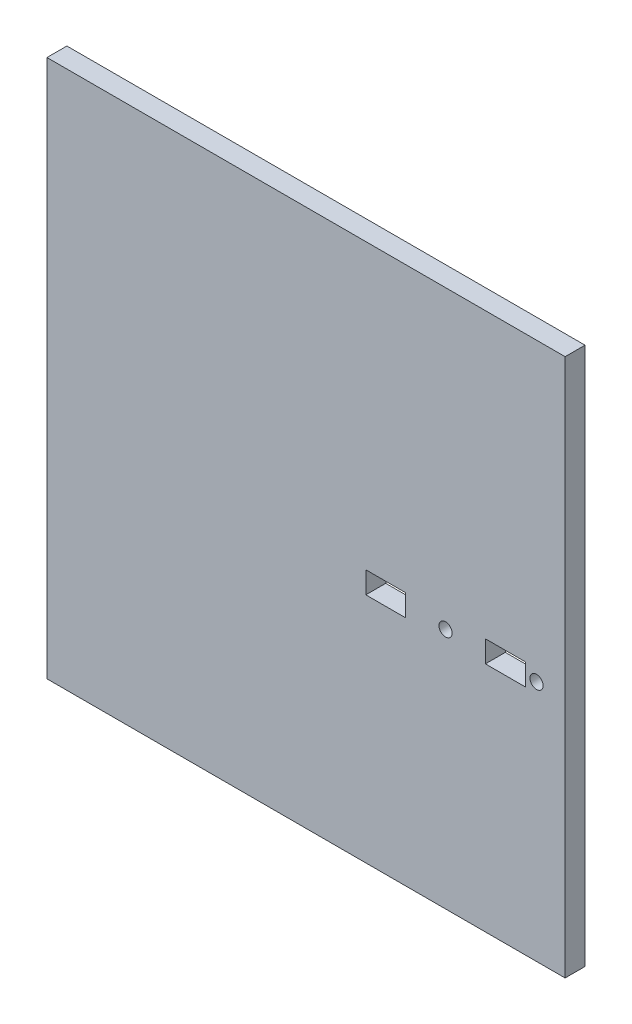
SolidWorks part; units mm, degrees
ref_plane "Front Plane" through (0, 0, 0) normal (0, 0, 1) x (1, 0, 0)
ref_plane "Top Plane" through (0, 0, 0) normal (0, 1, 0) x (1, 0, 0)
ref_plane "Right Plane" through (0, 0, 0) normal (1, 0, 0) x (0, 0, -1)
sketch "Sketch1" plane through (0, 0, 0) normal (0, 0, 1) x (1, 0, 0)
  line L0 (-6.35, 155.575) -> (-6.35, -15.875) construction
  line L1 (158.75, 155.575) -> (-6.35, 155.575)
  line L2 (158.75, 155.575) -> (158.75, -15.875)
  line L3 (158.75, -15.875) -> (-6.35, -15.875)
  line L4 (-6.35, 155.575) -> (-6.35, -15.875)
  line L6 (0, -15.875) -> (-6.35, -15.875) construction
extrude "Boss-Extrude1" add sketch "Sketch1" along normal blind 6.35
sketch "Sketch2" plane through (0, 0, 6.35) normal (0, 0, 1) x (1, 0, 0)
  line L0 (158.75, 40.3225) -> (69.85, 40.3225) construction
  line L1 (95.25, 65.0258) -> (107.95, 65.0258)
  line L2 (95.25, 65.0258) -> (95.25, 58.1025)
  line L3 (95.25, 58.1025) -> (107.95, 58.1025)
  line L4 (107.95, 65.0258) -> (107.95, 58.1025)
  line L5 (133.35, 65.0258) -> (146.05, 65.0258)
  line L6 (133.35, 65.0258) -> (133.35, 58.1025)
  line L7 (133.35, 58.1025) -> (146.05, 58.1025)
  line L8 (146.05, 65.0258) -> (146.05, 58.1025)
  line L9 (158.75, -15.875) -> (158.75, 155.575) construction
  dimension "D1" = 12.7
  dimension "D2" = 12.7
  dimension "D3" = 25.4
  dimension "D4" = 17.78
  dimension "D5" = 12.7
extrude "Cut-Extrude1" cut sketch "Sketch2" against normal blind 6.35
sketch "Sketch3" plane through (0, 0, 6.35) normal (0, 0, 1) x (1, 0, 0)
  line L0 (151.7657, 58.1025) -> (147.4985, 64.4525) construction
  line L1 (151.7657, 64.4525) -> (147.4985, 58.1025) construction
  line L2 (122.7836, 64.4525) -> (118.5164, 58.1025) construction
  line L3 (122.7836, 58.1025) -> (118.5164, 64.4525) construction
  circle A0 centre (120.65, 61.2775) radius 2.0955
  circle A1 centre (149.6321, 61.2775) radius 2.0955
  dimension "D1" = 4.191
extrude "Cut-Extrude2" cut sketch "Sketch3" against normal through all
